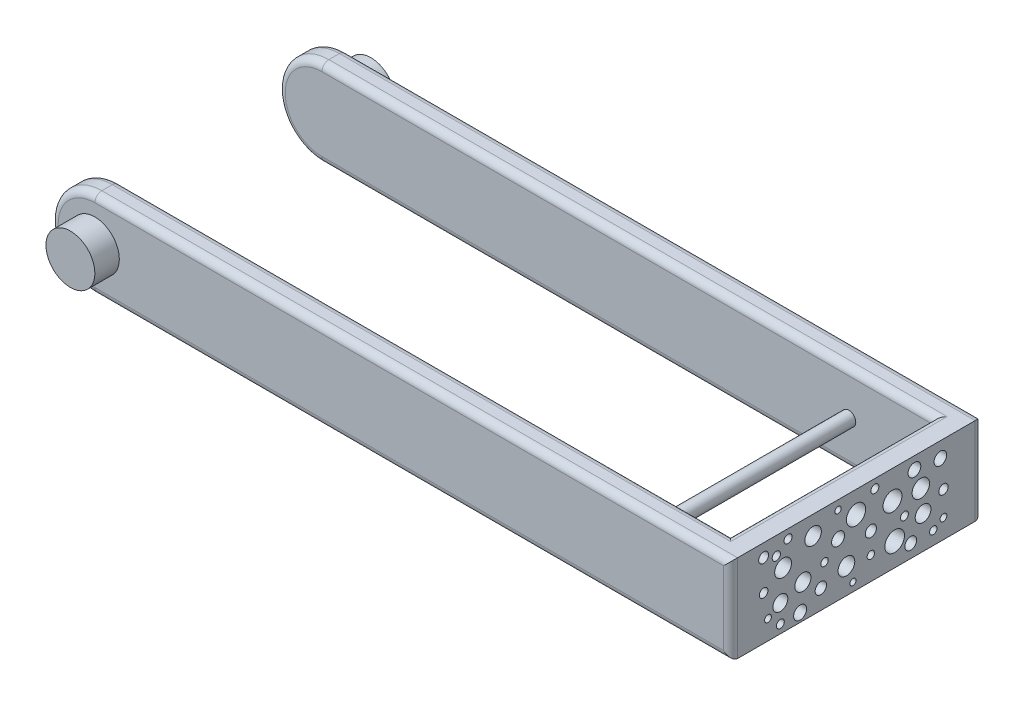
SolidWorks part; units mm, degrees
ref_plane "Front Plane" through (0, 0, 0) normal (0, 0, 1) x (1, 0, 0)
ref_plane "Top Plane" through (0, 0, 0) normal (0, 1, 0) x (1, 0, 0)
ref_plane "Right Plane" through (0, 0, 0) normal (1, 0, 0) x (0, 0, -1)
sketch "Sketch1" plane through (0, 0, 0) normal (0, 0, 1) x (1, 0, 0)
  line L0 (-87.5, 0) -> (87.5, 0) construction
  line L1 (-87.5, 12.5) -> (87.5, 12.5)
  line L2 (-87.5, -12.5) -> (87.5, -12.5)
  arc A0 (-87.5, 12.5) -> (-87.5, -12.5) centre (-87.5, 0) ccw
  arc A1 (87.5, -12.5) -> (87.5, 12.5) centre (87.5, 0) ccw
  point P2 (0, 0)
  dimension "D1" = 175
  dimension "D2" = 25
extrude "Boss-Extrude1" add sketch "Sketch1" along normal blind 7
ref_plane "Plane1" through (0, 0, 65) normal (0, 0, 1) x (1, 0, 0)
sketch "Sketch3" plane through (0, 0, 65) normal (0, 0, 1) x (1, 0, 0)
  line L0 (-87.5, 0) -> (87.5, 0) construction
  line L1 (-87.5, 12.5) -> (87.5, 12.5)
  line L2 (-87.5, -12.5) -> (87.5, -12.5)
  arc A0 (-87.5, 12.5) -> (-87.5, -12.5) centre (-87.5, 0) ccw
  arc A1 (87.5, -12.5) -> (87.5, 12.5) centre (87.5, 0) ccw
  point P2 (0, 0)
  dimension "D1" = 25
  dimension "D2" = 175
extrude "Boss-Extrude2" add sketch "Sketch3" along normal blind 7 separate body
sketch "Sketch4" plane through (0, 0, 72) normal (0, 0, 1) x (1, 0, 0)
  circle A0 centre (-87.5, 0) radius 7
  dimension "D1" = 14
extrude "Boss-Extrude3" add sketch "Sketch4" along normal blind 7
sketch "Sketch5" plane through (0, 0, 0) normal (0, 0, -1) x (-1, 0, 0)
  circle A0 centre (87.5, 0) radius 7
  dimension "D1" = 14
extrude "Boss-Extrude4" add sketch "Sketch5" along normal blind 7
sketch "Sketch6" plane through (0, 0, 0) normal (0, 0, 1) x (1, 0, 0)
  line L0 (87.5, 12.5) -> (87.5, -12.5)
  line L1 (87.5, -12.5) -> (103.1751, -12.5)
  line L2 (103.1751, -12.5) -> (103.1751, 12.5)
  line L3 (103.1751, 12.5) -> (87.5, 12.5)
extrude "Cut-Extrude1" cut sketch "Sketch6" along normal through all
sketch "Sketch7" plane through (87.5, 0, 0) normal (1, 0, 0) x (0, 0, -1)
  line L1 (-72, 12.5) -> (0, 12.5)
  line L2 (-72, 12.5) -> (-72, -12.5)
  line L3 (-72, -12.5) -> (0, -12.5)
  line L4 (0, 12.5) -> (0, -12.5)
extrude "Boss-Extrude5" add sketch "Sketch7" along normal blind 7
sketch "Sketch8" plane through (94.5, 0, 0) normal (1, 0, 0) x (0, 0, -1)
  circle A1 centre (-45.1101, -1.0171) radius 1.0614
  circle A2 centre (-31.843, 0.0442) radius 1.5921
  circle A3 centre (-25.6516, 4.3782) radius 2.7074
  circle A4 centre (-36.0884, 6.2356) radius 2.7547
  circle A5 centre (-48.3827, 7.0856) radius 2.3689
  circle A6 centre (-51.3014, -2.8745) radius 2.2996
  circle A7 centre (-38.8431, -5.1742) radius 2.3925
  circle A8 centre (-25.0325, -5.8818) radius 2.8151
  circle A9 centre (-22.2174, -1.0171) radius 1.1346
  circle A10 centre (-31.843, -5.8818) radius 1.0614
  circle A11 centre (-46.1715, -6.9431) radius 1.6309
  circle A12 centre (-56.9621, 3.4809) radius 2.4106
  circle A13 centre (-57.7581, -4.8204) radius 2.1393
  circle A14 centre (-41.2356, 2.7861) radius 1.8393
  circle A15 centre (-19.3719, 8.9902) radius 1.8242
  circle A16 centre (-17.5477, 3.4809) radius 2.4965
  circle A17 centre (-16.8953, -3.0667) radius 2.2528
  circle A19 centre (-13.9766, -8.7121) radius 1.0614
  circle A20 centre (-11.0578, 0) radius 1.3479
  circle A21 centre (-30.6931, 9.9504) radius 1.1498
  circle A23 centre (-41.2356, 9.9504) radius 0.9017
  circle A24 centre (-55.5469, 9.9504) radius 1.1498
  circle A25 centre (-36.9729, -10.0388) radius 0.8845
  circle A26 centre (-52.0975, -10.0388) radius 1.8574
  circle A27 centre (-20.4332, -8.7121) radius 1.699
  circle A28 centre (-11.9423, 8.093) radius 1.8099
  circle A29 centre (-11.0578, -7.0131) radius 0.9754
  circle A30 centre (-62.5343, 0.0442) radius 1.2383
  circle A31 centre (-61.296, -6.9431) radius 0.9754
  circle A32 centre (-62.5343, 8.8005) radius 1.4262
  circle A33 centre (-58.9079, 7.3744) radius 1.1855
  circle A34 centre (-57.7581, -10.0388) radius 1.1258
extrude "Cut-Extrude2" cut sketch "Sketch8" against normal blind 7
fillet "Fillet1" radius 2 16 edges at (3.5, -12.5, 0) (-100, 0, 0) (3.5, -12.5, 72) (-100, 0, 72) (0, -12.5, 65) (-100, 0, 65) (0, -12.5, 7) (-100, 0, 7) (87.5, -12.5, 36) (94.5, 0, 0) (94.5, 0, 72) (3.5, 12.5, 0) (3.5, 12.5, 72) (0, 12.5, 65) (0, 12.5, 7) (87.5, 12.5, 36)
sketch "Sketch9" plane through (0, 0, 72) normal (0, 0, 1) x (1, 0, 0)
  line L0 (0, 0) -> (92.5, 0) construction
  line L1 (92.5, -10.5) -> (92.5, 10.5) construction
  line L2 (92.5, 0) -> (97.2587, 2.313) construction
  line L3 (63.335, 10.5) -> (63.335, -10.5) construction
  line L4 (92.5, 10.5) -> (-87.5, 10.5) construction
  line L5 (-87.5, -10.5) -> (92.5, -10.5) construction
  circle A0 centre (63.335, 0) radius 2
  point P12 (63.335, 0)
  dimension "D1" = 4
extrude "Boss-Extrude6" add sketch "Sketch9" against normal blind 68
